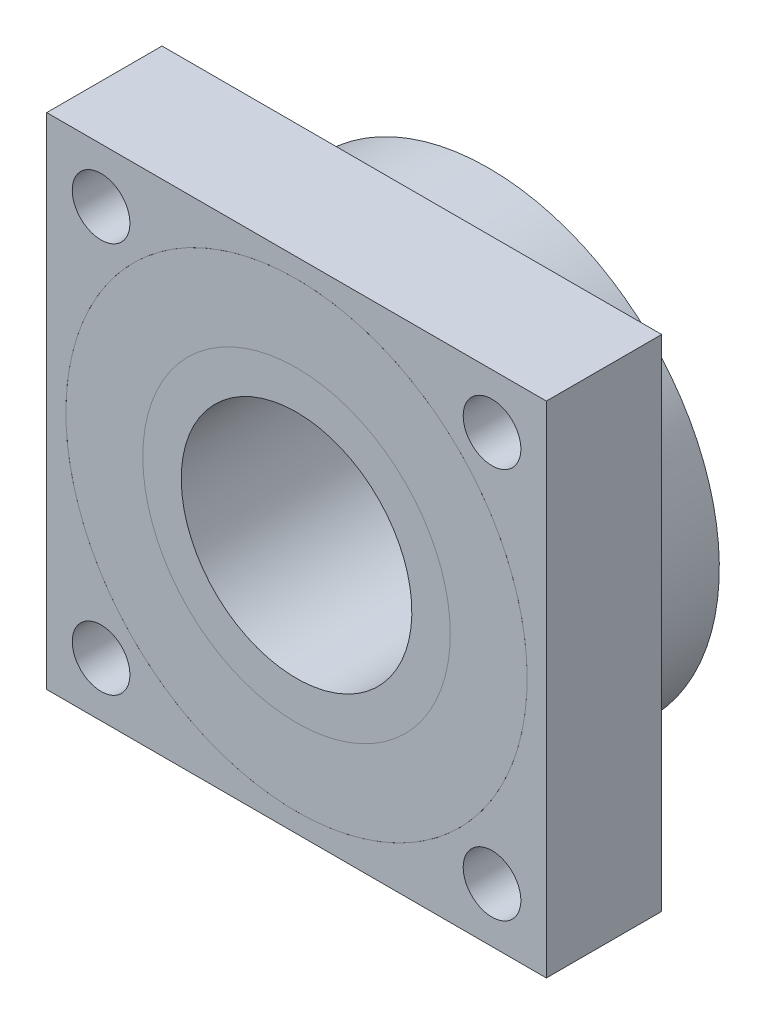
SolidWorks part; units mm, degrees
ref_plane "Front Plane" through (0, 0, 0) normal (0, 0, 1) x (1, 0, 0)
ref_plane "Top Plane" through (0, 0, 0) normal (0, 1, 0) x (1, 0, 0)
ref_plane "Right Plane" through (0, 0, 0) normal (1, 0, 0) x (0, 0, -1)
sketch "Sketch1" plane through (0, 0, 0) normal (1, 0, 0) x (0, 0, -1)
  line L0 (12.7, 0) -> (0, 0) construction
  line L1 (12.7, 0) -> (12.7, 10.16)
  line L2 (12.7, 10.16) -> (0, 10.16)
  line L3 (12.7, 0) -> (0, 0)
  line L4 (0, 10.16) -> (0, 0)
  line L5 (0, 7.62) -> (12.7, 7.62)
  line L6 (0, 10.16) -> (0, 15.24)
  line L7 (0, 15.24) -> (12.7, 15.24)
  line L8 (12.7, 15.24) -> (12.7, 10.16)
  dimension "D1" = 10.16
  dimension "D2" = 12.7
  dimension "D3" = 7.62
  dimension "D4" = 5.08
revolve "Revolve2" add sketch "Sketch1" angle 360 about L0 region at (0, 12.7, -6.35)
revolve "Revolve3" add sketch "Sketch1<4>" angle 360 about L0 region at (0, 8.89, -6.35)
sketch "Sketch1<4>" plane through (0, 0, 0) normal (1, 0, 0) x (0, 0, -1) same geometry as "Sketch1"
sketch "Sketch2" plane through (0, 0, 0) normal (0, 0, 1) x (1, 0, 0)
  circle A0 centre (0, 12.7) radius 1.905
  circle A1 centre (12.7, 0) radius 1.905
  circle A2 centre (0, -12.7) radius 1.905
  circle A3 centre (-12.7, 0) radius 1.905
  point P12 (0, 0)
  dimension "D1" = 3.81
  dimension "D2" = 12.7
  dimension "D3" = 4
sketch "Sketch3" plane through (0, 0, 0) normal (0, 0, 1) x (1, 0, 0)
  line L1 (-16.51, 16.51) -> (16.51, 16.51)
  line L2 (-16.51, 16.51) -> (-16.51, -16.51)
  line L3 (-16.51, -16.51) -> (16.51, -16.51)
  line L4 (16.51, 16.51) -> (16.51, -16.51)
  line L5 (-16.51, 16.51) -> (16.51, -16.51) construction
  line L6 (-16.51, -16.51) -> (16.51, 16.51) construction
  circle A0 centre (0, 0) radius 15.24
  circle A1 centre (0, 0) radius 15.24 construction
  point P0 (0, 0)
  dimension "D1" = 33.02
  dimension "D2" = 33.02
extrude "Boss-Extrude1" add sketch "Sketch3" against normal blind 7.62 separate body
sketch "Sketch4" plane through (0, 0, -7.62) normal (0, 0, -1) x (-1, 0, 0)
  line L0 (-16.51, 16.51) -> (0, 0) construction
  circle A0 centre (-12.9179, 12.9179) radius 1.905
  circle A1 centre (12.9179, 12.9179) radius 1.905
  circle A2 centre (12.9179, -12.9179) radius 1.905
  circle A3 centre (-12.9179, -12.9179) radius 1.905
  point P15 (0, 0)
  dimension "D1" = 3.81
  dimension "D2" = 5.08
  dimension "D3" = 4
extrude "Cut-Extrude2" cut sketch "Sketch4" against normal through all
